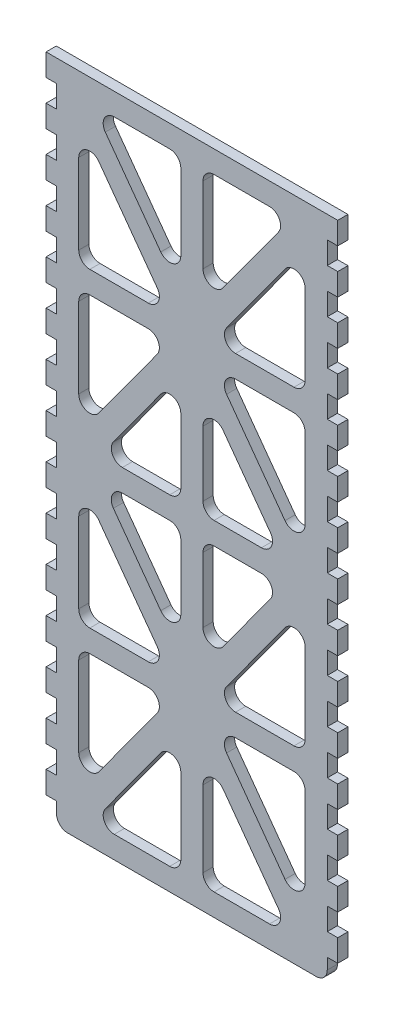
SolidWorks part; units mm, degrees
ref_plane "Front Plane" through (0, 0, 0) normal (0, 0, 1) x (1, 0, 0)
ref_plane "Top Plane" through (0, 0, 0) normal (0, 1, 0) x (1, 0, 0)
ref_plane "Right Plane" through (0, 0, 0) normal (1, 0, 0) x (0, 0, -1)
sketch "Sketch1" plane through (0, 0, 0) normal (0, 0, 1) x (1, 0, 0)
  line L1 (-38.735, 95.25) -> (38.735, 95.25)
  line L2 (-38.735, 95.25) -> (-38.735, -95.25)
  line L3 (-38.735, -95.25) -> (38.735, -95.25)
  line L4 (38.735, 95.25) -> (38.735, -95.25)
  point P4 (0, 95.25)
  point P6 (-38.735, 0)
  dimension "D1" = 77.47
  dimension "D2" = 190.5
extrude "Boss-Extrude1" add sketch "Sketch1" along normal mid plane 2.921
ref_plane "Plane1" through (0, 0, 0) normal (-1, 0, 0) x (0, 0, 1)
sketch "Sketch2" plane through (38.735, 0, 0) normal (1, 0, 0) x (0, 0, -1)
  line L0 (-1.4605, -95.25) -> (-1.4605, 95.25) construction
  line L1 (-1.4605, -82.55) -> (1.4605, -82.55)
  line L2 (-1.4605, -82.55) -> (-1.4605, -88.9)
  line L3 (-1.4605, -88.9) -> (1.4605, -88.9)
  line L4 (1.4605, -82.55) -> (1.4605, -88.9)
  line L5 (1.4605, -95.25) -> (1.4605, 95.25) construction
  line L6 (-1.4605, -95.25) -> (1.4605, -95.25) construction
  dimension "D1" = 6.35
  dimension "D2" = 6.35
extrude "Boss-Extrude2" add sketch "Sketch2" along normal blind 3
pattern_linear "LPattern1" count 15 spacing 12.7 along (0, 1, 0) of "Boss-Extrude2"
mirror "Mirror1" about plane through (0, 0, 0) normal (-1, 0, 0) of "LPattern1"
sketch "Sketch4" plane through (0, 0, 1.4605) normal (0, 0, 1) x (1, 0, 0)
  line L0 (41.735, 95.25) -> (-41.735, 95.25) construction
  line L1 (-38.735, -95.25) -> (38.735, -95.25) construction
  line L2 (-38.735, -95.25) -> (-38.735, 95.25) construction
  line L3 (-38.735, 95.25) -> (38.735, 95.25) construction
  line L4 (38.735, -95.25) -> (38.735, 95.25) construction
  line L5 (-38.735, -95.25) -> (38.735, -95.25) construction
  line L6 (-32.385, 0) -> (32.385, 0)
  line L7 (-32.385, 88.9) -> (32.385, 0)
  line L8 (32.385, 88.9) -> (-32.385, 0)
  line L9 (-32.385, 44.45) -> (32.385, 44.45)
  line L10 (0, 88.9) -> (0, 0)
  line L11 (0, 0) -> (0, -88.9)
  line L12 (-32.385, 0) -> (32.385, -88.9)
  line L13 (32.385, 0) -> (-32.385, -88.9)
  line L14 (-32.385, 88.9) -> (32.385, 88.9)
  line L15 (32.385, -88.9) -> (32.385, 88.9)
  line L16 (-32.385, -88.9) -> (32.385, -88.9)
  line L17 (-32.385, -88.9) -> (-32.385, 88.9)
  line L18 (32.385, -44.45) -> (-32.385, -44.45)
  line L19 (-29.8188, 1.8696) -> (34.9512, -87.0304)
  line L20 (34.9512, -1.8696) -> (-29.8188, -90.7696)
  line L21 (3.175, 88.9) -> (3.175, 0)
  line L22 (3.175, 0) -> (3.175, -88.9)
  line L23 (32.385, -47.625) -> (-32.385, -47.625)
  line L24 (34.9512, 87.0304) -> (-29.8188, -1.8696)
  line L25 (-29.8188, 90.7696) -> (34.9512, 1.8696)
  line L26 (-32.385, 47.625) -> (32.385, 47.625)
  line L27 (-32.385, 3.175) -> (32.385, 3.175)
  line L28 (-34.9512, -1.8696) -> (29.8188, -90.7696)
  line L29 (29.8188, 1.8696) -> (-34.9512, -87.0304)
  line L30 (-3.175, 88.9) -> (-3.175, 0)
  line L31 (-3.175, 0) -> (-3.175, -88.9)
  line L32 (32.385, -41.275) -> (-32.385, -41.275)
  line L33 (29.8188, 90.7696) -> (-34.9512, 1.8696)
  line L34 (-34.9512, 87.0304) -> (29.8188, -1.8696)
  line L35 (-32.385, 41.275) -> (32.385, 41.275)
  line L36 (-32.385, -3.175) -> (32.385, -3.175)
  point P24 (0, 44.45)
  point P25 (0, -44.45)
  dimension "D1" = 3.175
  dimension "D2" = 3.175
  dimension "D3" = 6.35
extrude "Cut-Extrude1" cut sketch "Sketch4" against normal through all contours L34 L17 L26 | L30 L14 L25 | L33 L14 L21 | L24 L26 L15 | L35 L25 L15 | L34 L21 L27 | L30 L24 L27 | L35 L17 L33 | L36 L19 L31 | L36 L22 L29 | L32 L15 L20 | L15 L23 L19 | L28 L22 L16 | L31 L20 L16 | L29 L23 L17 | L32 L28 L17 region at (-10.8312, 13.6835, 1.4605) region at (-10.8312, -13.6835, 1.4605) region at (10.8312, 13.6835, 1.4605) region at (10.8312, -13.6835, 1.4605) region at (-23.6705, -29.3139, 1.4605) region at (-23.6705, 29.3139, 1.4605) region at (23.6705, -29.3139, 1.4605) region at (23.6705, 29.3139, 1.4605) region at (-23.6705, -59.5861, 1.4605) region at (-23.6705, 59.5861, 1.4605) region at (23.6705, 59.5861, 1.4605) region at (-11.6022, 77.3332, 1.4605) region at (11.6022, 77.3332, 1.4605) region at (-11.6022, -77.3332, 1.4605) region at (11.6022, -77.3332, 1.4605) region at (23.6705, -59.5861, 1.4605)
fillet "Fillet1" radius 3.175 50 edges at (38.735, -95.25, 0) (-38.735, -95.25, 0) (26.1435, 3.175, 0) (3.175, 3.175, 0) (3.175, 34.7004, 0) (-6.2415, 41.275, 0) (-32.385, 5.3918, 0) (-32.385, 41.275, 0) (-3.175, 54.1996, 0) (-28.4567, 88.9, 0) (-3.175, 88.9, 0) (32.385, 41.275, 0) (32.385, 5.3918, 0) (6.2415, 41.275, 0) (26.1435, -3.175, 0) (3.175, -34.7004, 0) (3.175, -3.175, 0) (-32.385, -83.5082, 0) (-32.385, -47.625, 0) (-6.2415, -47.625, 0) (-32.385, -41.275, 0) (-32.385, -5.3918, 0) (-6.2415, -41.275, 0) (-6.2415, 47.625, 0) (-32.385, 47.625, 0) (-32.385, 83.5082, 0) (-3.175, -88.9, 0) (-28.4567, -88.9, 0) (-3.175, -54.1996, 0) (6.2415, -47.625, 0) (32.385, -47.625, 0) (28.4567, -88.9, 0) (3.175, -88.9, 0) (3.175, -54.1996, 0) (6.2415, -41.275, 0) (32.385, -5.3918, 0) (32.385, -41.275, 0) (32.385, 47.625, 0) (6.2415, 47.625, 0) (32.385, 83.5082, 0) (3.175, 54.1996, 0) (3.175, 88.9, 0) (28.4567, 88.9, 0) (-3.175, -3.175, 0) (-3.175, -34.7004, 0) (-26.1435, -3.175, 0) (-3.175, 3.175, 0) (-26.1435, 3.175, 0) (-3.175, 34.7004, 0) (32.385, -83.5082, 0)
